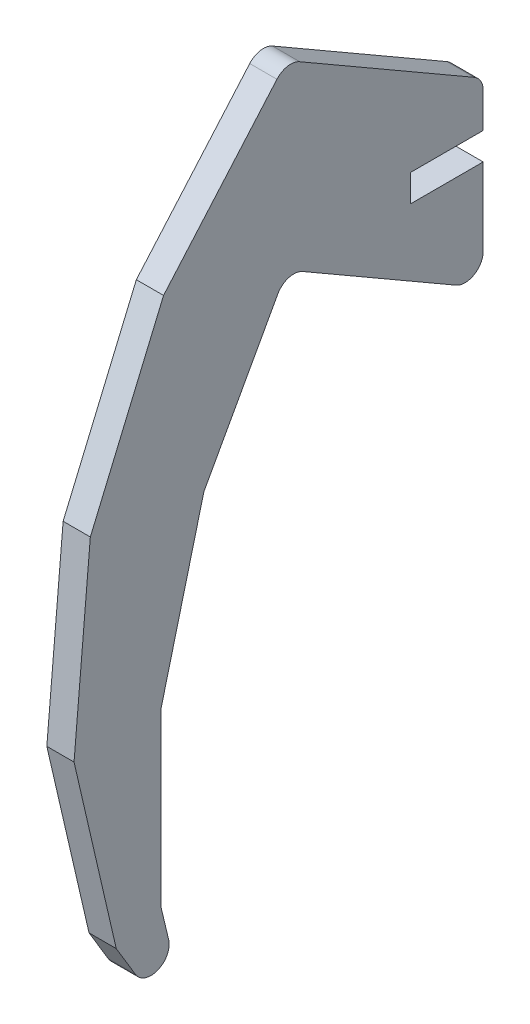
SolidWorks part; units mm, degrees
ref_plane "Front Plane" through (0, 0, 0) normal (0, 0, 1) x (1, 0, 0)
ref_plane "Top Plane" through (0, 0, 0) normal (0, 1, 0) x (1, 0, 0)
ref_plane "Right Plane" through (0, 0, 0) normal (1, 0, 0) x (0, 0, -1)
sketch "Sketch1" plane through (0, 0, 0) normal (1, 0, 0) x (0, 0, -1)
  line L0 (0, 0) -> (0, 20) construction
  line L1 (0, 0) -> (0, -70) construction
  line L2 (0, -70) -> (-10, -70) construction
  line L3 (-13.869, -53.8469) -> (-13.0192, -57.3951)
  line L4 (1.4281, 19.1755) -> (20.6506, 8.0774)
  line L5 (1.7674, -1.0204) -> (18.6506, -10.7679)
  line L6 (21.6506, 6.3453) -> (21.6506, 2.5)
  line L7 (-0.9845, -1.7876) -> (-9.1328, -16.5827)
  line L8 (-1.0816, 18.7552) -> (-13.5801, 4.3705)
  line L9 (-13.5801, 4.3705) -> (-21.65, -14.6534)
  line L10 (-21.65, -14.6534) -> (-23.4462, -35.24)
  line L11 (-23.4462, -35.24) -> (-18.7929, -55.374)
  line L12 (-18.7929, -55.374) -> (-16.6782, -58.8915)
  line L13 (-9.1328, -16.5827) -> (-13.8547, -34.9156)
  line L14 (-13.8547, -34.9156) -> (-13.869, -53.8469)
  line L15 (21.6506, -0.5) -> (21.6506, -9.0359)
  line L16 (21.6506, 2.5) -> (13.6506, 2.5)
  line L18 (21.6506, -0.5) -> (13.6506, -0.5)
  line L19 (13.6506, 2.5) -> (13.6506, -0.5)
  line L28 (58.4047, 33.4739) -> (48.1115, 34.372) [skipped]
  line L29 (37.8182, 35.2701) -> (27.7512, 32.9435) [skipped]
  line L30 (17.6842, 30.6168) -> (8.8289, 25.2932) [skipped]
  line L31 (77.4286, 25.4041) -> (67.9167, 29.439) [skipped]
  line L32 (93.0277, 11.8504) -> (85.2282, 18.6272) [skipped]
  line L33 (103.675, -5.8602) -> (98.3514, 2.9951) [skipped]
  line L34 (105.8571, -15.3019) -> (103.5305, -5.2349) [skipped]
  line L35 (0.0225, -80.1816) -> (7.822, -86.9584) [skipped]
  line L36 (7.4535, -86.6383) -> (16.9654, -90.6732) [skipped]
  line L37 (26.4774, -94.7081) -> (36.7707, -95.6062) [skipped]
  line L38 (57.9453, -93.9895) -> (68.0123, -91.6628) [skipped]
  line L39 (76.8103, -86.0723) -> (85.6657, -80.7486) [skipped]
  line L40 (92.2664, -72.7356) -> (99.0432, -64.936) [skipped]
  line L41 (98.4622, -65.6047) -> (102.4972, -56.0927) [skipped]
  line L42 (106.5321, -46.5808) -> (107.4302, -36.2875) [skipped]
  line L66 (28.9617, 23.9222) -> (20.9657, 18.8564) [skipped]
  line L67 (46.9708, 29.7587) -> (37.9663, 26.8405) [skipped]
  line L68 (65.8656, 30.9331) -> (56.4182, 30.3459) [skipped]
  line L69 (84.4589, 27.3716) -> (75.1623, 29.1523) [skipped]
  line L70 (116.1599, 7.2198) -> (108.8711, 13.2589) [skipped]
  line L71 (127.2759, -8.1044) -> (121.7179, -0.4423) [skipped]
  line L72 (134.2316, -25.7115) -> (127.2759, -8.1044) [skipped]
  line L73 (136.5901, -44.4953) -> (134.2316, -25.7115) [skipped]
  line L74 (101.5823, 19.2981) -> (93.0206, 23.3348) [skipped]
  line L75 (134.2031, -63.2755) -> (135.3966, -53.8854) [skipped]
  line L76 (20.8698, -107.6716) -> (28.8581, -112.7496) [skipped]
  line L77 (75.0507, -118.0497) -> (84.35, -116.2831) [skipped]
  line L78 (92.9178, -112.2593) -> (101.4856, -108.2355) [skipped]
  line L79 (108.7836, -102.2074) -> (116.0816, -96.1793) [skipped]
  line L80 (116.0816, -96.1793) -> (127.2207, -80.872) [skipped]
  line L81 (130.7119, -72.0738) -> (134.2031, -63.2755) [skipped]
  line L82 (46.8584, -118.6133) -> (56.3049, -119.2148) [skipped]
  line L83 (37.8582, -115.6815) -> (46.8584, -118.6133) [skipped]
  line L84 (-0.0673, -88.7835) -> (6.4071, -95.6885) [skipped]
  line L85 (-9.1749, -72.187) -> (-4.6211, -80.4852) [skipped]
  line L86 (-13.869, -53.8469) -> (-11.522, -63.0169) [skipped]
  line L87 (9.0855, 9.6604) -> (6.4849, 6.8952) [skipped]
  arc A0 (18.6506, -10.7679) -> (21.6506, -9.0359) centre (19.6506, -9.0359) ccw
  arc A1 (20.6506, 8.0774) -> (21.6506, 6.3453) centre (19.6506, 6.3453) cw
  arc A2 (-13.0192, -57.3951) -> (-16.6782, -58.8915) centre (-14.9641, -57.861) cw
  arc A3 (-0.9845, -1.7876) -> (1.7674, -1.0204) centre (0.7674, -2.7524) cw
  arc A4 (1.4281, 19.1755) -> (-1.0816, 18.7552) centre (0.4281, 17.4434) ccw
  point P19 (21.6506, -12.5)
  point P23 (21.6506, 7.5)
  dimension "D9" = 2
  dimension "D1" = 20
  dimension "D2" = 70
  dimension "D3" = 60
  dimension "D4" = 10
  dimension "D5" = 20
  dimension "D6" = 8
  dimension "D7" = 3
  dimension "D8" = 5
extrude "Boss-Extrude1" add sketch "Sketch1" along normal blind 3
